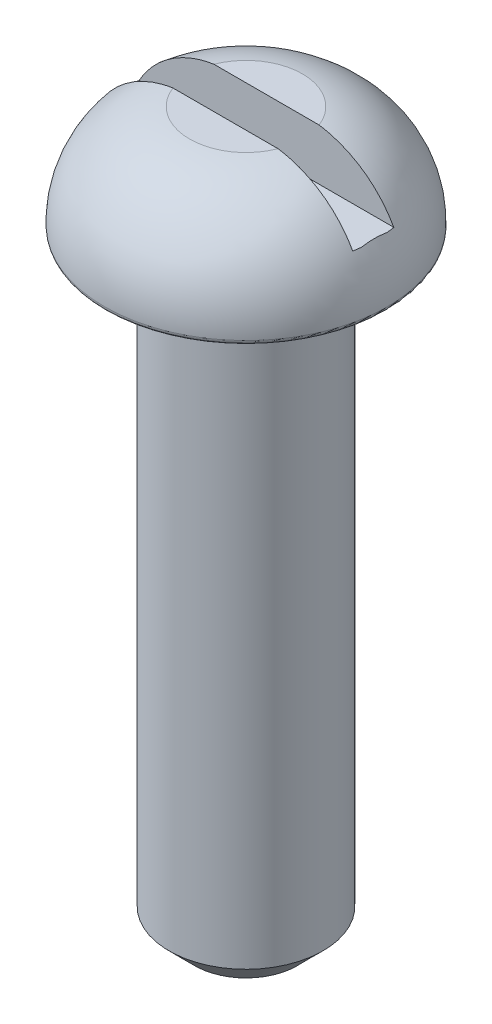
SolidWorks part; units mm, degrees
ref_plane "Спереди" through (0, 0, 0) normal (0, 0, 1) x (1, 0, 0)
ref_plane "Сверху" through (0, 0, 0) normal (0, 1, 0) x (1, 0, 0)
ref_plane "Справа" through (0, 0, 0) normal (1, 0, 0) x (0, 0, -1)
sketch "Эскиз1" plane through (0, 0, 0) normal (0, 0, 1) x (1, 0, 0)
  line L0 (2.75, 11.9) -> (1.5, 11.9)
  line L1 (0, 0) -> (0, 14)
  line L2 (1.5, 11.9) -> (1.5, 0.5)
  line L3 (1.5, 0.5) -> (1, 0)
  line L4 (1, 0) -> (0, 0)
  line L5 (0, 14) -> (1.1, 14)
  arc A0 (1.1, 14) -> (2.75, 11.9) centre (0.7797, 12.0501) cw
  dimension "D2" = 1.1
  dimension "D8" = 2.1
  dimension "D1" = 14
  dimension "D3" = 1.5
  dimension "D4" = 1
  dimension "D5" = 2.1
  dimension "D6" = 2.75
  dimension "D7" = 45
  dimension "D9" = 1.5
  dimension "D10" = 11.9
revolve "Повернуть1" add sketch "Эскиз1" angle 360 about L1
fillet "Скругление1" radius 0.1 1 edges at (0, 11.9, -2.75)
sketch "Эскиз3" plane through (0, 14, 0) normal (0, 1, 0) x (-1, 0, 0)
  line L1 (2.5, -0.4) -> (-2.5, -0.4)
  line L2 (2.5, -0.4) -> (2.5, 0.4)
  line L3 (2.5, 0.4) -> (-2.5, 0.4)
  line L4 (-2.5, -0.4) -> (-2.5, 0.4)
  dimension "D1" = 0.8
  dimension "D2" = 0.4
  dimension "D3" = 5
  dimension "D4" = 2.5
extrude "Вырез-Вытянуть2" cut sketch "Эскиз3" against normal blind 1
ref_axis "Ось1" through (0, -104.1565, 0) along (0, 1, 0)
